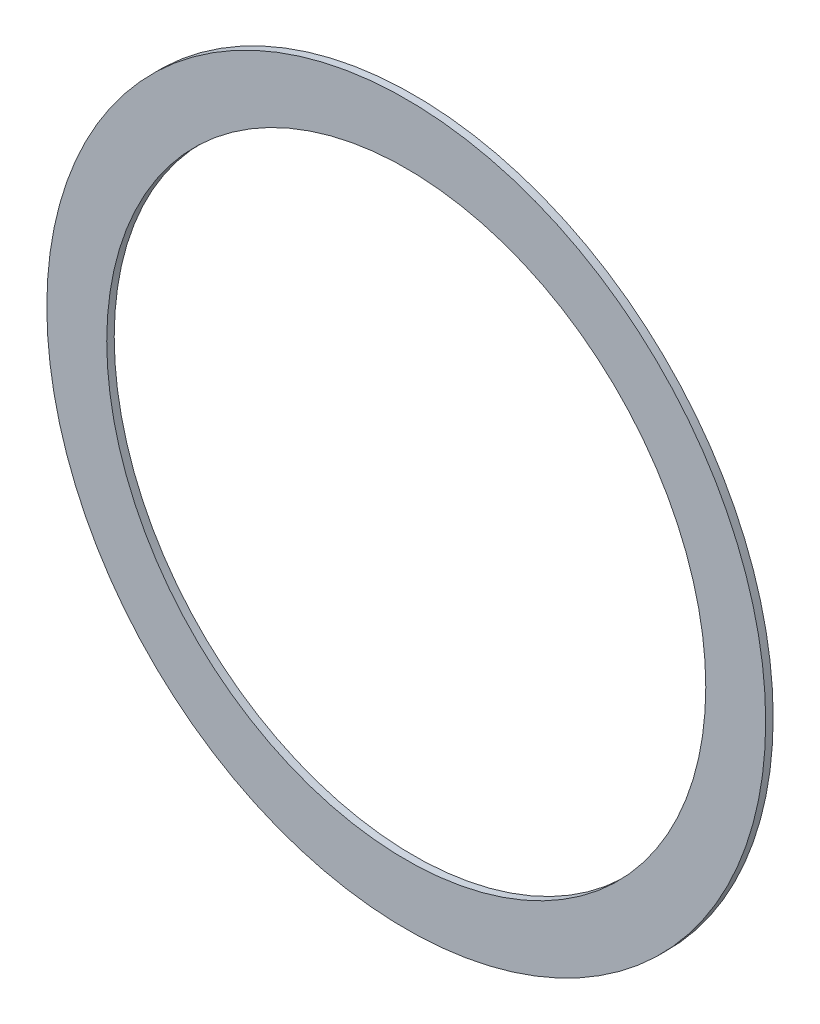
SolidWorks part; units mm, degrees
ref_plane "Front Plane" through (0, 0, 0) normal (0, 0, 1) x (1, 0, 0)
ref_plane "Top Plane" through (0, 0, 0) normal (0, 1, 0) x (1, 0, 0)
ref_plane "Right Plane" through (0, 0, 0) normal (1, 0, 0) x (0, 0, -1)
sketch "Sketch1" plane through (0, 0, 0) normal (0, 0, 1) x (1, 0, 0)
  circle A0 centre (0, 0) radius 20
  circle A1 centre (0, 0) radius 24
extrude "Boss-Extrude1" add sketch "Sketch1" along normal blind 0.5
